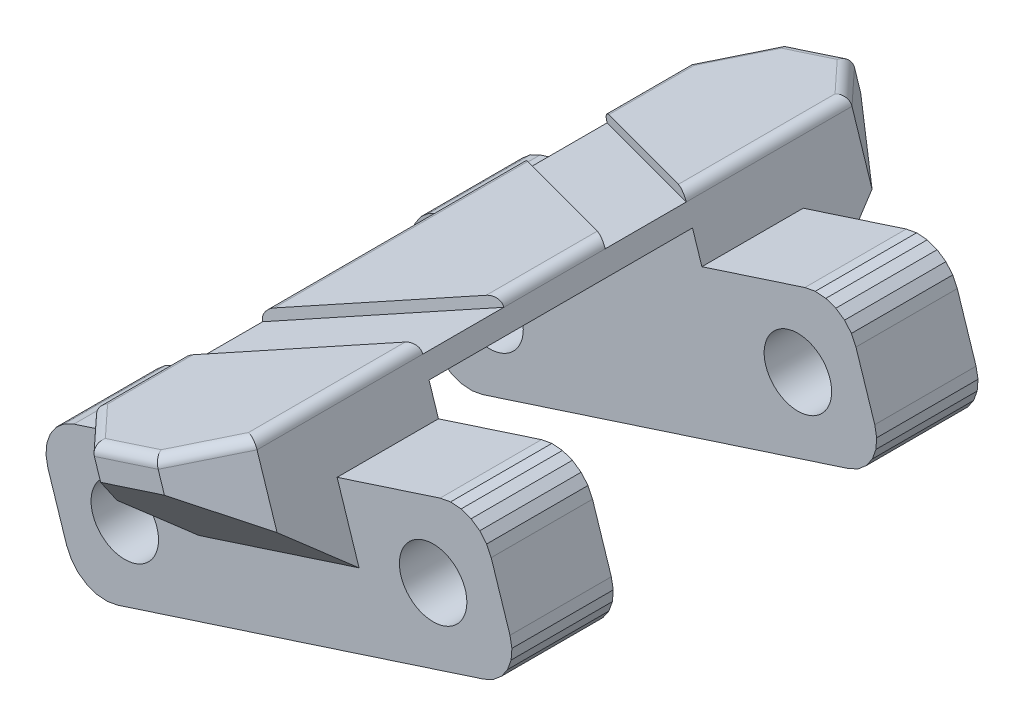
SolidWorks part; units mm, degrees
ref_plane "Front Plane" through (0, 0, 0) normal (0, 0, 1) x (1, 0, 0)
ref_plane "Top Plane" through (0, 0, 0) normal (0, 1, 0) x (1, 0, 0)
ref_plane "Right Plane" through (0, 0, 0) normal (1, 0, 0) x (0, 0, -1)
sketch "Model" plane through (0, 0, 0) normal (0, 0, 1) x (1, 0, 0)
  line L0 (68.3376, 63.8225) -> (68.8552, 63.8907) construction
  line L1 (68.8552, 63.8907) -> (69.3376, 64.0905) construction
  line L2 (69.3376, 64.0905) -> (69.7518, 64.4083) construction
  line L3 (69.7518, 64.4083) -> (70.0696, 64.8225) construction
  line L4 (70.0696, 64.8225) -> (70.2694, 65.3049) construction
  line L5 (70.2694, 65.3049) -> (70.3376, 65.8225) construction
  line L6 (70.3376, 65.8225) -> (70.3376, 68.8225) construction
  line L7 (70.3376, 68.8225) -> (70.2694, 69.3401) construction
  line L8 (70.2694, 69.3401) -> (70.0696, 69.8225) construction
  line L9 (70.0696, 69.8225) -> (69.7518, 70.2367) construction
  line L10 (69.7518, 70.2367) -> (69.3376, 70.5546) construction
  line L11 (69.3376, 70.5546) -> (68.8552, 70.7544) construction
  line L12 (68.8552, 70.7544) -> (68.3376, 70.8225) construction
  line L13 (68.3376, 70.8225) -> (49.3376, 70.8225) construction
  line L14 (49.3376, 70.8225) -> (48.8199, 70.7544) construction
  line L15 (48.8199, 70.7544) -> (48.3376, 70.5546) construction
  line L16 (48.3376, 70.5546) -> (47.9233, 70.2367) construction
  line L17 (47.9233, 70.2367) -> (47.6055, 69.8225) construction
  line L18 (47.6055, 69.8225) -> (47.4057, 69.3401) construction
  line L19 (47.4057, 69.3401) -> (47.3376, 68.8225) construction
  line L20 (47.3376, 68.8225) -> (47.3376, 65.8225) construction
  line L21 (47.3376, 65.8225) -> (47.4057, 65.3049) construction
  line L22 (47.4057, 65.3049) -> (47.6055, 64.8225) construction
  line L23 (47.6055, 64.8225) -> (47.9233, 64.4083) construction
  line L24 (47.9233, 64.4083) -> (48.3376, 64.0905) construction
  line L25 (48.3376, 64.0905) -> (48.8199, 63.8907) construction
  line L26 (48.8199, 63.8907) -> (49.3376, 63.8225) construction
  line L27 (49.3376, 63.8225) -> (68.3376, 63.8225) construction
  line L28 (100.3376, 63.8225) -> (100.8552, 63.8907) construction
  line L29 (100.8552, 63.8907) -> (101.3376, 64.0905) construction
  line L30 (101.3376, 64.0905) -> (101.7518, 64.4083) construction
  line L31 (101.7518, 64.4083) -> (102.0696, 64.8225) construction
  line L32 (102.0696, 64.8225) -> (102.2694, 65.3049) construction
  line L33 (102.2694, 65.3049) -> (102.3376, 65.8225) construction
  line L34 (102.3376, 65.8225) -> (102.3376, 68.8225) construction
  line L35 (102.3376, 68.8225) -> (102.2694, 69.3401) construction
  line L36 (102.2694, 69.3401) -> (102.0696, 69.8225) construction
  line L37 (102.0696, 69.8225) -> (101.7518, 70.2367) construction
  line L38 (101.7518, 70.2367) -> (101.3376, 70.5546) construction
  line L39 (101.3376, 70.5546) -> (100.8552, 70.7544) construction
  line L40 (100.8552, 70.7544) -> (100.3376, 70.8225) construction
  line L41 (100.3376, 70.8225) -> (81.3376, 70.8225) construction
  line L42 (81.3376, 70.8225) -> (80.8199, 70.7544) construction
  line L43 (80.8199, 70.7544) -> (80.3376, 70.5546) construction
  line L44 (80.3376, 70.5546) -> (79.9233, 70.2367) construction
  line L45 (79.9233, 70.2367) -> (79.6055, 69.8225) construction
  line L46 (79.6055, 69.8225) -> (79.4057, 69.3401) construction
  line L47 (79.4057, 69.3401) -> (79.3376, 68.8225) construction
  line L48 (79.3376, 68.8225) -> (79.3376, 65.8225) construction
  line L49 (79.3376, 65.8225) -> (79.4057, 65.3049) construction
  line L50 (79.4057, 65.3049) -> (79.6055, 64.8225) construction
  line L51 (79.6055, 64.8225) -> (79.9233, 64.4083) construction
  line L52 (79.9233, 64.4083) -> (80.3376, 64.0905) construction
  line L53 (80.3376, 64.0905) -> (80.8199, 63.8907) construction
  line L54 (80.8199, 63.8907) -> (81.3376, 63.8225) construction
  line L55 (81.3376, 63.8225) -> (100.3376, 63.8225) construction
  line L56 (132.3376, 63.8225) -> (132.8552, 63.8907) construction
  line L57 (132.8552, 63.8907) -> (133.3376, 64.0905) construction
  line L58 (133.3376, 64.0905) -> (133.7518, 64.4083) construction
  line L59 (133.7518, 64.4083) -> (134.0696, 64.8225) construction
  line L60 (134.0696, 64.8225) -> (134.2694, 65.3049) construction
  line L61 (134.2694, 65.3049) -> (134.3376, 65.8225) construction
  line L62 (134.3376, 65.8225) -> (134.3376, 68.8225) construction
  line L63 (134.3376, 68.8225) -> (134.2694, 69.3401) construction
  line L64 (134.2694, 69.3401) -> (134.0696, 69.8225) construction
  line L65 (134.0696, 69.8225) -> (133.7518, 70.2367) construction
  line L66 (133.7518, 70.2367) -> (133.3376, 70.5546) construction
  line L67 (133.3376, 70.5546) -> (132.8552, 70.7544) construction
  line L68 (132.8552, 70.7544) -> (132.3376, 70.8225) construction
  line L69 (132.3376, 70.8225) -> (113.3376, 70.8225) construction
  line L70 (113.3376, 70.8225) -> (112.8199, 70.7544) construction
  line L71 (112.8199, 70.7544) -> (112.3376, 70.5546) construction
  line L72 (112.3376, 70.5546) -> (111.9233, 70.2367) construction
  line L73 (111.9233, 70.2367) -> (111.6055, 69.8225) construction
  line L74 (111.6055, 69.8225) -> (111.4057, 69.3401) construction
  line L75 (111.4057, 69.3401) -> (111.3376, 68.8225) construction
  line L76 (111.3376, 68.8225) -> (111.3376, 65.8225) construction
  line L77 (111.3376, 65.8225) -> (111.4057, 65.3049) construction
  line L78 (111.4057, 65.3049) -> (111.6055, 64.8225) construction
  line L79 (111.6055, 64.8225) -> (111.9233, 64.4083) construction
  line L80 (111.9233, 64.4083) -> (112.3376, 64.0905) construction
  line L81 (112.3376, 64.0905) -> (112.8199, 63.8907) construction
  line L82 (112.8199, 63.8907) -> (113.3376, 63.8225) construction
  line L83 (113.3376, 63.8225) -> (132.3376, 63.8225) construction
  line L84 (164.3376, 63.8225) -> (164.8552, 63.8907) construction
  line L85 (164.8552, 63.8907) -> (165.3376, 64.0905) construction
  line L86 (165.3376, 64.0905) -> (165.7518, 64.4083) construction
  line L87 (165.7518, 64.4083) -> (166.0696, 64.8225) construction
  line L88 (166.0696, 64.8225) -> (166.2694, 65.3049) construction
  line L89 (166.2694, 65.3049) -> (166.3376, 65.8225) construction
  line L90 (166.3376, 65.8225) -> (166.3376, 68.8225) construction
  line L91 (166.3376, 68.8225) -> (166.2694, 69.3401) construction
  line L92 (166.2694, 69.3401) -> (166.0696, 69.8225) construction
  line L93 (166.0696, 69.8225) -> (165.7518, 70.2367) construction
  line L94 (165.7518, 70.2367) -> (165.3376, 70.5546) construction
  line L95 (165.3376, 70.5546) -> (164.8552, 70.7544) construction
  line L96 (164.8552, 70.7544) -> (164.3376, 70.8225) construction
  line L97 (164.3376, 70.8225) -> (145.3376, 70.8225) construction
  line L98 (145.3376, 70.8225) -> (144.8199, 70.7544) construction
  line L99 (144.8199, 70.7544) -> (144.3376, 70.5546) construction
  line L100 (144.3376, 70.5546) -> (143.9233, 70.2367) construction
  line L101 (143.9233, 70.2367) -> (143.6055, 69.8225) construction
  line L102 (143.6055, 69.8225) -> (143.4057, 69.3401) construction
  line L103 (143.4057, 69.3401) -> (143.3376, 68.8225) construction
  line L104 (143.3376, 68.8225) -> (143.3376, 65.8225) construction
  line L105 (143.3376, 65.8225) -> (143.4057, 65.3049) construction
  line L106 (143.4057, 65.3049) -> (143.6055, 64.8225) construction
  line L107 (143.6055, 64.8225) -> (143.9233, 64.4083) construction
  line L108 (143.9233, 64.4083) -> (144.3376, 64.0905) construction
  line L109 (144.3376, 64.0905) -> (144.8199, 63.8907) construction
  line L110 (144.8199, 63.8907) -> (145.3376, 63.8225) construction
  line L111 (145.3376, 63.8225) -> (164.3376, 63.8225) construction
  line L112 (55.5729, 2.088) -> (56.0906, 2.1561) construction
  line L113 (56.0906, 2.1561) -> (56.5729, 2.3559) construction
  line L114 (56.5729, 2.3559) -> (56.9871, 2.6738) construction
  line L115 (56.9871, 2.6738) -> (57.305, 3.088) construction
  line L116 (57.305, 3.088) -> (57.5048, 3.5703) construction
  line L117 (57.5048, 3.5703) -> (57.5729, 4.088) construction
  line L118 (57.5729, 4.088) -> (57.5729, 7.088) construction
  line L119 (57.5729, 7.088) -> (57.5048, 7.6056) construction
  line L120 (57.5048, 7.6056) -> (57.305, 8.088) construction
  line L121 (57.305, 8.088) -> (56.9871, 8.5022) construction
  line L122 (56.9871, 8.5022) -> (56.5729, 8.82) construction
  line L123 (56.5729, 8.82) -> (56.0906, 9.0198) construction
  line L124 (56.0906, 9.0198) -> (55.5729, 9.088) construction
  line L125 (55.5729, 9.088) -> (36.5729, 9.088) construction
  line L126 (36.5729, 9.088) -> (36.0553, 9.0198) construction
  line L127 (36.0553, 9.0198) -> (35.5729, 8.82) construction
  line L128 (35.5729, 8.82) -> (35.1587, 8.5022) construction
  line L129 (35.1587, 8.5022) -> (34.8409, 8.088) construction
  line L130 (34.8409, 8.088) -> (34.6411, 7.6056) construction
  line L131 (34.6411, 7.6056) -> (34.5729, 7.088) construction
  line L132 (34.5729, 7.088) -> (34.5729, 4.088) construction
  line L133 (34.5729, 4.088) -> (34.6411, 3.5703) construction
  line L134 (34.6411, 3.5703) -> (34.8409, 3.088) construction
  line L135 (34.8409, 3.088) -> (35.1587, 2.6738) construction
  line L136 (35.1587, 2.6738) -> (35.5729, 2.3559) construction
  line L137 (35.5729, 2.3559) -> (36.0553, 2.1561) construction
  line L138 (36.0553, 2.1561) -> (36.5729, 2.088) construction
  line L139 (36.5729, 2.088) -> (55.5729, 2.088) construction
  line L140 (87.5729, 2.088) -> (88.0906, 2.1561) construction
  line L141 (88.0906, 2.1561) -> (88.5729, 2.3559) construction
  line L142 (88.5729, 2.3559) -> (88.9871, 2.6738) construction
  line L143 (88.9871, 2.6738) -> (89.305, 3.088) construction
  line L144 (89.305, 3.088) -> (89.5048, 3.5703) construction
  line L145 (89.5048, 3.5703) -> (89.5729, 4.088) construction
  line L146 (89.5729, 4.088) -> (89.5729, 7.088) construction
  line L147 (89.5729, 7.088) -> (89.5048, 7.6056) construction
  line L148 (89.5048, 7.6056) -> (89.305, 8.088) construction
  line L149 (89.305, 8.088) -> (88.9871, 8.5022) construction
  line L150 (88.9871, 8.5022) -> (88.5729, 8.82) construction
  line L151 (88.5729, 8.82) -> (88.0906, 9.0198) construction
  line L152 (88.0906, 9.0198) -> (87.5729, 9.088) construction
  line L153 (87.5729, 9.088) -> (68.5729, 9.088) construction
  line L154 (68.5729, 9.088) -> (68.0553, 9.0198) construction
  line L155 (68.0553, 9.0198) -> (67.5729, 8.82) construction
  line L156 (67.5729, 8.82) -> (67.1587, 8.5022) construction
  line L157 (67.1587, 8.5022) -> (66.8409, 8.088) construction
  line L158 (66.8409, 8.088) -> (66.6411, 7.6056) construction
  line L159 (66.6411, 7.6056) -> (66.5729, 7.088) construction
  line L160 (66.5729, 7.088) -> (66.5729, 4.088) construction
  line L161 (66.5729, 4.088) -> (66.6411, 3.5703) construction
  line L162 (66.6411, 3.5703) -> (66.8409, 3.088) construction
  line L163 (66.8409, 3.088) -> (67.1587, 2.6738) construction
  line L164 (67.1587, 2.6738) -> (67.5729, 2.3559) construction
  line L165 (67.5729, 2.3559) -> (68.0553, 2.1561) construction
  line L166 (68.0553, 2.1561) -> (68.5729, 2.088) construction
  line L167 (68.5729, 2.088) -> (87.5729, 2.088) construction
  line L168 (119.5729, 2.088) -> (120.0906, 2.1561) construction
  line L169 (120.0906, 2.1561) -> (120.5729, 2.3559) construction
  line L170 (120.5729, 2.3559) -> (120.9871, 2.6738) construction
  line L171 (120.9871, 2.6738) -> (121.305, 3.088) construction
  line L172 (121.305, 3.088) -> (121.5048, 3.5703) construction
  line L173 (121.5048, 3.5703) -> (121.5729, 4.088) construction
  line L174 (121.5729, 4.088) -> (121.5729, 7.088) construction
  line L175 (121.5729, 7.088) -> (121.5048, 7.6056) construction
  line L176 (121.5048, 7.6056) -> (121.305, 8.088) construction
  line L177 (121.305, 8.088) -> (120.9871, 8.5022) construction
  line L178 (120.9871, 8.5022) -> (120.5729, 8.82) construction
  line L179 (120.5729, 8.82) -> (120.0906, 9.0198) construction
  line L180 (120.0906, 9.0198) -> (119.5729, 9.088) construction
  line L181 (119.5729, 9.088) -> (100.5729, 9.088) construction
  line L182 (100.5729, 9.088) -> (100.0553, 9.0198) construction
  line L183 (100.0553, 9.0198) -> (99.5729, 8.82) construction
  line L184 (99.5729, 8.82) -> (99.1587, 8.5022) construction
  line L185 (99.1587, 8.5022) -> (98.8409, 8.088) construction
  line L186 (98.8409, 8.088) -> (98.6411, 7.6056) construction
  line L187 (98.6411, 7.6056) -> (98.5729, 7.088) construction
  line L188 (98.5729, 7.088) -> (98.5729, 4.088) construction
  line L189 (98.5729, 4.088) -> (98.6411, 3.5703) construction
  line L190 (98.6411, 3.5703) -> (98.8409, 3.088) construction
  line L191 (98.8409, 3.088) -> (99.1587, 2.6738) construction
  line L192 (99.1587, 2.6738) -> (99.5729, 2.3559) construction
  line L193 (99.5729, 2.3559) -> (100.0553, 2.1561) construction
  line L194 (100.0553, 2.1561) -> (100.5729, 2.088) construction
  line L195 (100.5729, 2.088) -> (119.5729, 2.088) construction
  line L196 (151.5729, 2.088) -> (152.0906, 2.1561) construction
  line L197 (152.0906, 2.1561) -> (152.5729, 2.3559) construction
  line L198 (152.5729, 2.3559) -> (152.9871, 2.6738) construction
  line L199 (152.9871, 2.6738) -> (153.305, 3.088) construction
  line L200 (153.305, 3.088) -> (153.5048, 3.5703) construction
  line L201 (153.5048, 3.5703) -> (153.5729, 4.088) construction
  line L202 (153.5729, 4.088) -> (153.5729, 7.088) construction
  line L203 (153.5729, 7.088) -> (153.5048, 7.6056) construction
  line L204 (153.5048, 7.6056) -> (153.305, 8.088) construction
  line L205 (153.305, 8.088) -> (152.9871, 8.5022) construction
  line L206 (152.9871, 8.5022) -> (152.5729, 8.82) construction
  line L207 (152.5729, 8.82) -> (152.0906, 9.0198) construction
  line L208 (152.0906, 9.0198) -> (151.5729, 9.088) construction
  line L209 (151.5729, 9.088) -> (132.5729, 9.088) construction
  line L210 (132.5729, 9.088) -> (132.0553, 9.0198) construction
  line L211 (132.0553, 9.0198) -> (131.5729, 8.82) construction
  line L212 (131.5729, 8.82) -> (131.1587, 8.5022) construction
  line L213 (131.1587, 8.5022) -> (130.8409, 8.088) construction
  line L214 (130.8409, 8.088) -> (130.6411, 7.6056) construction
  line L215 (130.6411, 7.6056) -> (130.5729, 7.088) construction
  line L216 (130.5729, 7.088) -> (130.5729, 4.088) construction
  line L217 (130.5729, 4.088) -> (130.6411, 3.5703) construction
  line L218 (130.6411, 3.5703) -> (130.8409, 3.088) construction
  line L219 (130.8409, 3.088) -> (131.1587, 2.6738) construction
  line L220 (131.1587, 2.6738) -> (131.5729, 2.3559) construction
  line L221 (131.5729, 2.3559) -> (132.0553, 2.1561) construction
  line L222 (132.0553, 2.1561) -> (132.5729, 2.088) construction
  line L223 (132.5729, 2.088) -> (151.5729, 2.088) construction
  line L224 (17.1125, 65.2434) -> (16.6413, 65.0186)
  line L225 (16.6413, 65.0186) -> (16.2442, 64.6796)
  line L226 (16.2442, 64.6796) -> (15.9485, 64.2493)
  line L227 (15.9485, 64.2493) -> (15.7742, 63.7571)
  line L228 (15.7742, 63.7571) -> (15.7333, 63.2366)
  line L229 (15.7333, 63.2366) -> (15.8284, 62.7233)
  line L230 (15.8284, 62.7233) -> (16.7555, 59.8701)
  line L231 (16.7555, 59.8701) -> (16.9802, 59.3988)
  line L232 (16.9802, 59.3988) -> (17.3193, 59.0018)
  line L233 (17.3193, 59.0018) -> (17.7496, 58.7061)
  line L234 (17.7496, 58.7061) -> (18.2418, 58.5318)
  line L235 (18.2418, 58.5318) -> (18.7623, 58.4909)
  line L236 (18.7623, 58.4909) -> (19.2756, 58.586)
  line L237 (19.2756, 58.586) -> (37.3457, 64.4573)
  line L238 (37.3457, 64.4573) -> (37.8169, 64.6821)
  line L239 (37.8169, 64.6821) -> (38.214, 65.0212)
  line L240 (38.214, 65.0212) -> (38.5097, 65.4515)
  line L241 (38.5097, 65.4515) -> (38.684, 65.9436)
  line L242 (38.684, 65.9436) -> (38.7249, 66.4641)
  line L243 (38.7249, 66.4641) -> (38.6298, 66.9775)
  line L244 (38.6298, 66.9775) -> (37.7027, 69.8306)
  line L245 (37.7027, 69.8306) -> (37.478, 70.3019)
  line L246 (37.478, 70.3019) -> (37.1389, 70.6989)
  line L247 (37.1389, 70.6989) -> (36.7086, 70.9946)
  line L248 (36.7086, 70.9946) -> (36.2164, 71.1689)
  line L249 (36.2164, 71.1689) -> (35.6959, 71.2099)
  line L250 (35.6959, 71.2099) -> (35.1826, 71.1147)
  line L251 (35.1826, 71.1147) -> (17.1125, 65.2434)
  line L252 (1.8526, 34.098) -> (1.8116, 33.5775) construction
  line L253 (1.8116, 33.5775) -> (1.9068, 33.0642) construction
  line L254 (1.9068, 33.0642) -> (2.1315, 32.5929) construction
  line L255 (2.1315, 32.5929) -> (2.4706, 32.1959) construction
  line L256 (2.4706, 32.1959) -> (2.9009, 31.9002) construction
  line L257 (2.9009, 31.9002) -> (3.3931, 31.7259) construction
  line L258 (3.3931, 31.7259) -> (6.3275, 31.1022) construction
  line L259 (6.3275, 31.1022) -> (6.848, 31.0612) construction
  line L260 (6.848, 31.0612) -> (7.3614, 31.1564) construction
  line L261 (7.3614, 31.1564) -> (7.8326, 31.3811) construction
  line L262 (7.8326, 31.3811) -> (8.2296, 31.7202) construction
  line L263 (8.2296, 31.7202) -> (8.5253, 32.1505) construction
  line L264 (8.5253, 32.1505) -> (8.6996, 32.6426) construction
  line L265 (8.6996, 32.6426) -> (12.6499, 51.2274) construction
  line L266 (12.6499, 51.2274) -> (12.6909, 51.7479) construction
  line L267 (12.6909, 51.7479) -> (12.5958, 52.2613) construction
  line L268 (12.5958, 52.2613) -> (12.371, 52.7325) construction
  line L269 (12.371, 52.7325) -> (12.0319, 53.1296) construction
  line L270 (12.0319, 53.1296) -> (11.6016, 53.4253) construction
  line L271 (11.6016, 53.4253) -> (11.1095, 53.5996) construction
  line L272 (11.1095, 53.5996) -> (8.175, 54.2233) construction
  line L273 (8.175, 54.2233) -> (7.5501, 54.256) construction
  line L274 (7.5501, 54.256) -> (6.9457, 54.0941) construction
  line L275 (6.9457, 54.0941) -> (6.4209, 53.7533) construction
  line L276 (6.4209, 53.7533) -> (6.0272, 53.267) construction
  line L277 (6.0272, 53.267) -> (5.8029, 52.6828) construction
  line L278 (5.8029, 52.6828) -> (1.8526, 34.098) construction
  line L279 (21.1953, 5.3099) -> (21.6256, 5.0141) construction
  line L280 (21.6256, 5.0141) -> (22.1178, 4.8399) construction
  line L281 (22.1178, 4.8399) -> (22.6383, 4.7989) construction
  line L282 (22.6383, 4.7989) -> (23.1516, 4.894) construction
  line L283 (23.1516, 4.894) -> (23.6229, 5.1188) construction
  line L284 (23.6229, 5.1188) -> (24.0199, 5.4579) construction
  line L285 (24.0199, 5.4579) -> (26.0273, 7.6873) construction
  line L286 (26.0273, 7.6873) -> (26.323, 8.1176) construction
  line L287 (26.323, 8.1176) -> (26.4973, 8.6098) construction
  line L288 (26.4973, 8.6098) -> (26.5382, 9.1303) construction
  line L289 (26.5382, 9.1303) -> (26.4431, 9.6436) construction
  line L290 (26.4431, 9.6436) -> (26.2183, 10.1149) construction
  line L291 (26.2183, 10.1149) -> (25.8792, 10.5119) construction
  line L292 (25.8792, 10.5119) -> (11.7595, 23.2254) construction
  line L293 (11.7595, 23.2254) -> (11.3292, 23.5211) construction
  line L294 (11.3292, 23.5211) -> (10.837, 23.6954) construction
  line L295 (10.837, 23.6954) -> (10.3166, 23.7363) construction
  line L296 (10.3166, 23.7363) -> (9.8032, 23.6412) construction
  line L297 (9.8032, 23.6412) -> (9.3319, 23.4164) construction
  line L298 (9.3319, 23.4164) -> (8.9349, 23.0773) construction
  line L299 (8.9349, 23.0773) -> (6.9275, 20.8479) construction
  line L300 (6.9275, 20.8479) -> (6.6318, 20.4176) construction
  line L301 (6.6318, 20.4176) -> (6.4575, 19.9255) construction
  line L302 (6.4575, 19.9255) -> (6.4166, 19.405) construction
  line L303 (6.4166, 19.405) -> (6.5117, 18.8916) construction
  line L304 (6.5117, 18.8916) -> (6.7365, 18.4203) construction
  line L305 (6.7365, 18.4203) -> (7.0756, 18.0233) construction
  line L306 (7.0756, 18.0233) -> (21.1953, 5.3099) construction
  circle A0 centre (50.8376, 67.3225) radius 1.5 construction
  circle A1 centre (66.8376, 67.3225) radius 1.5 construction
  circle A2 centre (82.8376, 67.3225) radius 1.5 construction
  circle A3 centre (98.8376, 67.3225) radius 1.5 construction
  circle A4 centre (114.8376, 67.3225) radius 1.5 construction
  circle A5 centre (130.8376, 67.3225) radius 1.5 construction
  circle A6 centre (146.8376, 67.3225) radius 1.5 construction
  circle A7 centre (162.8376, 67.3225) radius 1.5 construction
  circle A8 centre (38.0729, 5.588) radius 1.5 construction
  circle A9 centre (54.0729, 5.588) radius 1.5 construction
  circle A10 centre (70.0729, 5.588) radius 1.5 construction
  circle A11 centre (86.0729, 5.588) radius 1.5 construction
  circle A12 centre (102.0729, 5.588) radius 1.5 construction
  circle A13 centre (118.0729, 5.588) radius 1.5 construction
  circle A14 centre (134.0729, 5.588) radius 1.5 construction
  circle A15 centre (150.0729, 5.588) radius 1.5 construction
  circle A16 centre (34.8376, 67.3225) radius 1.665
  circle A17 centre (19.6206, 62.3782) radius 1.665
  circle A18 centre (8.9146, 50.4879) radius 1.5 construction
  circle A19 centre (5.588, 34.8376) radius 1.5 construction
  circle A20 centre (10.5322, 19.6206) radius 1.5 construction
  circle A21 centre (22.4226, 8.9146) radius 1.5 construction
extrude "Boss-Extrude1" add sketch "Model" along normal blind 5
sketch "Sketch2" plane through (-17.5404, 53.9841, 0) normal (-0.309, 0.9511, 0) x (0.9511, 0.309, 0)
  line L0 (45.9362, 0) -> (45.9362, -5) construction
  line L1 (55.4362, 0) -> (36.4362, 0) construction
  line L2 (55.4362, -5) -> (36.4362, -5) construction
  line L4 (50.0914, 0) -> (41.781, 0)
  line L5 (50.0914, 0) -> (50.0914, -5)
  line L6 (50.0914, -5) -> (41.781, -5)
  line L7 (41.781, 0) -> (41.781, -5)
  line L8 (50.0914, 0) -> (41.781, -5) construction
  line L9 (50.0914, -5) -> (41.781, 0) construction
  point P6 (45.9362, -2.5)
extrude "Boss-Extrude2" add sketch "Sketch2" along normal blind 1.5
sketch "Sketch3" plane through (-18.0039, 55.4106, 0) normal (-0.309, 0.9511, 0) x (0.9511, 0.309, 0)
  line L0 (41.781, 0) -> (41.781, -5)
  line L1 (41.781, 0) -> (50.0914, 0)
  line L2 (50.0914, 0) -> (50.0914, -5)
  line L3 (45.9362, -5) -> (45.9362, -18) construction
  line L4 (41.781, -5) -> (50.0914, -5) construction
  line L5 (45.9362, -11.5) -> (35.5041, -11.5) construction
  line L6 (41.781, -5) -> (41.781, -11.5)
  line L7 (41.781, -11.5) -> (50.0914, -11.5)
  line L8 (50.0914, -11.5) -> (50.0914, -5)
extrude "Boss-Extrude3" add sketch "Sketch3" along normal blind 1.5
ref_plane "Plane1" through (0, 0, 11.5) normal (0, 0, 1) x (1, 0, 0)
mirror "Mirror4" about plane through (0, 0, 11.5) normal (0, 0, 1) of "Boss-Extrude2", "Boss-Extrude3", "Boss-Extrude1"
mirror "Mirror5" about plane through (0, 0, 11.5) normal (0, 0, 1) of "Boss-Extrude2", "Boss-Extrude1"
mirror "Mirror8" about plane through (0, 0, 11.5) normal (0, 0, 1) of "Boss-Extrude1"
sketch "Sketch5" plane through (0, 0, 0) normal (0, 0, -1) x (-1, 0, 0)
  line L0 (-29.1724, 72.3163) -> (-29.6359, 70.8897)
  line L1 (-29.1724, 72.3163) -> (-30.0994, 69.4631) construction
  line L2 (-29.6359, 70.8897) -> (-21.7322, 68.3216)
  line L3 (-21.2686, 69.7482) -> (-22.1957, 66.895) construction
  line L4 (-21.7322, 68.3216) -> (-21.2686, 69.7482)
  line L5 (-21.2686, 69.7482) -> (-29.1724, 72.3163)
extrude "Boss-Extrude4" add sketch "Sketch5" along normal blind 5.68
mirror "Mirror9" about plane through (0, 0, 11.5) normal (0, 0, 1) of "Boss-Extrude4"
sketch "Sketch7" plane through (47.6398, 15.479, 0) normal (0.9511, 0.309, 0) x (0, 0, -1)
  line L0 (5.68, 58.2622) -> (0, 58.2622)
  line L1 (0, 58.2622) -> (0, 53.2622)
  line L2 (0, 53.2622) -> (5.68, 58.2622)
extrude "Boss-Extrude5" add sketch "Sketch7" against normal blind 8.31
mirror "Mirror10" about plane through (0, 0, 11.5) normal (0, 0, 1) of "Boss-Extrude5"
sketch "Sketch8" plane through (-18.4674, 56.8372, 0) normal (-0.309, 0.9511, 0) x (0.9511, 0.309, 0)
  line L0 (41.781, -11.5) -> (50.0914, -11.5) construction
  line L1 (41.781, 5.68) -> (41.781, -28.68) construction
  line L2 (50.0914, -28.68) -> (50.0914, 5.68) construction
  line L3 (45.9362, -11.5) -> (45.9362, -7) construction
  line L4 (45.9362, -7) -> (50.0914, -9)
  line L5 (50.0914, -9) -> (50.0914, -5)
  line L6 (50.0914, -5) -> (50.0914, 0) construction
  line L7 (45.9362, -7) -> (41.781, -5)
  line L8 (41.781, -5) -> (36.4362, -5) construction
  line L9 (41.781, -5) -> (41.781, -1)
  line L10 (41.781, -1) -> (50.0914, -5)
extrude "Cut-Extrude1" cut sketch "Sketch8" against normal blind 0.5
mirror "Mirror11" about plane through (0, 0, 11.5) normal (0, 0, 1) of "Cut-Extrude1"
chamfer "Chamfer1" distance 2.5 angle 45 4 edges at (21.5004, 69.0349, 28.68) (29.4041, 71.603, 28.68) (29.4041, 71.603, -5.68) (21.5004, 69.0349, -5.68)
fillet "Fillet1" radius 0.5 20 edges at (29.1724, 72.3163, 0.91) (21.2686, 69.7482, 11.5) (21.3459, 69.5104, 5) (21.3459, 69.5104, 1) (29.2496, 72.0785, 5) (29.2496, 72.0785, 9) (29.1724, 72.3163, 11.5) (21.2686, 69.7482, 24.09) (21.3459, 69.5104, 18) (29.2496, 72.0785, 14) (29.2496, 72.0785, 18) (21.3459, 69.5104, 22) (21.2686, 69.7482, -1.09) (25.2205, 71.0322, 28.68) (29.1724, 72.3163, 22.09) (27.9835, 71.93, 27.43) (22.4575, 70.1345, 27.43) (25.2205, 71.0322, -5.68) (22.4575, 70.1345, -4.43) (27.9835, 71.93, -4.43)
